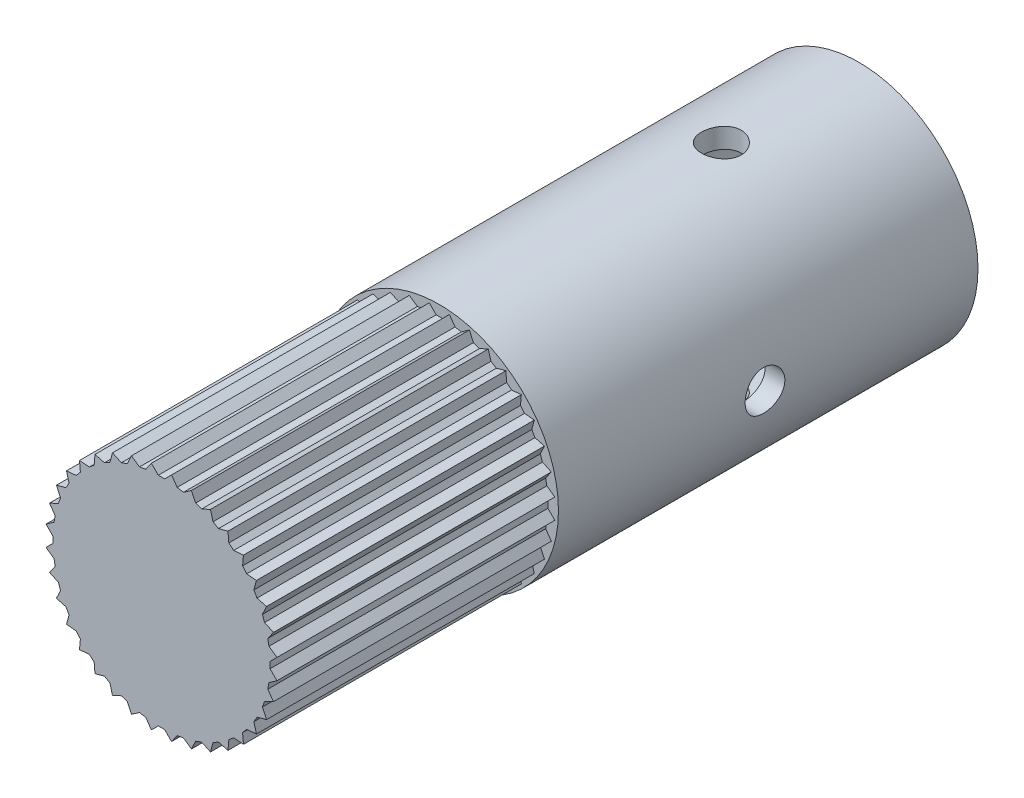
SolidWorks part; units mm, degrees
material "AISI 1015 Steel, Cold Drawn (SS)"
ref_plane "X-Y Datum" through (0, 0, 0) normal (0, 0, 1) x (1, 0, 0)
ref_plane "X-Z Datum" through (0, 0, 0) normal (0, 1, 0) x (1, 0, 0)
ref_plane "Y-Z Datum" through (0, 0, 0) normal (1, 0, 0) x (0, 0, -1)
sketch "Sketch9" plane through (0, 0, 0) normal (0, 1, 0) x (1, 0, 0)
  line L0 (16.002, 0) -> (0, 0)
  line L1 (0, 0) -> (0, -389.0916)
  line L2 (0, -389.0916) -> (-72.2493, -524.9728)
  dimension "D1" = 153.895
  dimension "D2" = 28
  dimension "D3" = 389.0916
  dimension "D5" = 16.002
sketch "Sketch5" plane through (0, 0, 0) normal (0, 1, 0) x (1, 0, 0)
  line L0 (7.9375, -77.9416) -> (7.9375, -22.1615)
  line L1 (7.9375, -22.1615) -> (9.525, -22.1615)
  line L2 (9.525, -22.1615) -> (9.525, -77.9416)
  line L3 (9.525, -77.9416) -> (7.9375, -77.9416)
  line L5 (16.002, 0) -> (0, 0) construction
  line L6 (0, 0) -> (0, -389.0916) construction
  line L7 (0, -389.0916) -> (9.525, -389.0916) construction
  line L8 (12.5602, -58.6916) -> (0, -58.6916) construction
  dimension "D1" = 1.5875
  dimension "D2" = 22.1615
  dimension "D3" = 7.9375
  dimension "D4" = 330.4
  dimension "D5" = 311.15
revolve "Revolve2" add sketch "Sketch5" angle 360 about L1
sketch "Sketch6" plane through (0, 0, 0) normal (0, 1, 0) x (1, 0, 0)
  circle A0 centre (0, -33.1635) radius 1.5875 construction
  circle A1 centre (0, -33.1635) radius 1.5875
sketch "Sketch7" plane through (0, 0, 0) normal (1, 0, 0) x (0, 0, -1)
  circle A2 centre (-39.196, 0) radius 1.5875
  circle A4 centre (-39.196, 0) radius 1.5875 construction
extrude "Cut-Extrude5" cut sketch "Sketch7" against normal through all both and the other way through all
extrude "Cut-Extrude6" cut sketch "Sketch6" against normal through all both and the other way through all
sketch "Sketch8" plane through (0, 0, 0) normal (0, 0, 1) x (1, 0, 0)
  line L0 (9.2357, -0.808) -> (8.6817, -0.254)
  line L1 (8.6817, -0.254) -> (8.6817, 0.254)
  line L2 (8.6817, 0.254) -> (9.2357, 0.808)
  line L3 (8.6817, 0) -> (0, 0) construction
  line L4 (8.9551, -2.3995) -> (8.5057, -1.7577)
  line L5 (8.5057, -1.7577) -> (8.5939, -1.2574)
  line L6 (8.5939, -1.2574) -> (9.2357, -0.808)
  line L7 (8.4024, -3.9181) -> (8.0713, -3.208)
  line L8 (8.0713, -3.208) -> (8.245, -2.7306)
  line L9 (8.245, -2.7306) -> (8.9551, -2.3995)
  line L10 (7.5944, -5.3176) -> (7.3916, -4.5608)
  line L11 (7.3916, -4.5608) -> (7.6456, -4.1209)
  line L12 (7.6456, -4.1209) -> (8.4024, -3.9181)
  line L13 (6.5556, -6.5556) -> (6.4873, -5.7751)
  line L14 (6.4873, -5.7751) -> (6.8138, -5.3859)
  line L15 (6.8138, -5.3859) -> (7.5944, -5.3176)
  line L16 (5.3176, -7.5944) -> (5.3859, -6.8138)
  line L17 (5.3859, -6.8138) -> (5.7751, -6.4873)
  line L18 (5.7751, -6.4873) -> (6.5556, -6.5556)
  line L19 (3.9181, -8.4024) -> (4.1209, -7.6456)
  line L20 (4.1209, -7.6456) -> (4.5608, -7.3916)
  line L21 (4.5608, -7.3916) -> (5.3176, -7.5944)
  line L22 (2.3995, -8.9551) -> (2.7306, -8.245)
  line L23 (2.7306, -8.245) -> (3.208, -8.0713)
  line L24 (3.208, -8.0713) -> (3.9181, -8.4024)
  line L25 (0.808, -9.2357) -> (1.2574, -8.5939)
  line L26 (1.2574, -8.5939) -> (1.7577, -8.5057)
  line L27 (1.7577, -8.5057) -> (2.3995, -8.9551)
  line L28 (-0.808, -9.2357) -> (-0.254, -8.6817)
  line L29 (-0.254, -8.6817) -> (0.254, -8.6817)
  line L30 (0.254, -8.6817) -> (0.808, -9.2357)
  line L31 (-2.3995, -8.9551) -> (-1.7577, -8.5057)
  line L32 (-1.7577, -8.5057) -> (-1.2574, -8.5939)
  line L33 (-1.2574, -8.5939) -> (-0.808, -9.2357)
  line L34 (-3.9181, -8.4024) -> (-3.208, -8.0713)
  line L35 (-3.208, -8.0713) -> (-2.7306, -8.245)
  line L36 (-2.7306, -8.245) -> (-2.3995, -8.9551)
  line L37 (-5.3176, -7.5944) -> (-4.5608, -7.3916)
  line L38 (-4.5608, -7.3916) -> (-4.1209, -7.6456)
  line L39 (-4.1209, -7.6456) -> (-3.9181, -8.4024)
  line L40 (-6.5556, -6.5556) -> (-5.7751, -6.4873)
  line L41 (-5.7751, -6.4873) -> (-5.3859, -6.8138)
  line L42 (-5.3859, -6.8138) -> (-5.3176, -7.5944)
  line L43 (-7.5944, -5.3176) -> (-6.8138, -5.3859)
  line L44 (-6.8138, -5.3859) -> (-6.4873, -5.7751)
  line L45 (-6.4873, -5.7751) -> (-6.5556, -6.5556)
  line L46 (-8.4024, -3.9181) -> (-7.6456, -4.1209)
  line L47 (-7.6456, -4.1209) -> (-7.3916, -4.5608)
  line L48 (-7.3916, -4.5608) -> (-7.5944, -5.3176)
  line L49 (-8.9551, -2.3995) -> (-8.245, -2.7306)
  line L50 (-8.245, -2.7306) -> (-8.0713, -3.208)
  line L51 (-8.0713, -3.208) -> (-8.4024, -3.9181)
  line L52 (-9.2357, -0.808) -> (-8.5939, -1.2574)
  line L53 (-8.5939, -1.2574) -> (-8.5057, -1.7577)
  line L54 (-8.5057, -1.7577) -> (-8.9551, -2.3995)
  line L55 (-9.2357, 0.808) -> (-8.6817, 0.254)
  line L56 (-8.6817, 0.254) -> (-8.6817, -0.254)
  line L57 (-8.6817, -0.254) -> (-9.2357, -0.808)
  line L58 (-8.9551, 2.3995) -> (-8.5057, 1.7577)
  line L59 (-8.5057, 1.7577) -> (-8.5939, 1.2574)
  line L60 (-8.5939, 1.2574) -> (-9.2357, 0.808)
  line L61 (-8.4024, 3.9181) -> (-8.0713, 3.208)
  line L62 (-8.0713, 3.208) -> (-8.245, 2.7306)
  line L63 (-8.245, 2.7306) -> (-8.9551, 2.3995)
  line L64 (-7.5944, 5.3176) -> (-7.3916, 4.5608)
  line L65 (-7.3916, 4.5608) -> (-7.6456, 4.1209)
  line L66 (-7.6456, 4.1209) -> (-8.4024, 3.9181)
  line L67 (-6.5556, 6.5556) -> (-6.4873, 5.7751)
  line L68 (-6.4873, 5.7751) -> (-6.8138, 5.3859)
  line L69 (-6.8138, 5.3859) -> (-7.5944, 5.3176)
  line L70 (-5.3176, 7.5944) -> (-5.3859, 6.8138)
  line L71 (-5.3859, 6.8138) -> (-5.7751, 6.4873)
  line L72 (-5.7751, 6.4873) -> (-6.5556, 6.5556)
  line L73 (-3.9181, 8.4024) -> (-4.1209, 7.6456)
  line L74 (-4.1209, 7.6456) -> (-4.5608, 7.3916)
  line L75 (-4.5608, 7.3916) -> (-5.3176, 7.5944)
  line L76 (-2.3995, 8.9551) -> (-2.7306, 8.245)
  line L77 (-2.7306, 8.245) -> (-3.208, 8.0713)
  line L78 (-3.208, 8.0713) -> (-3.9181, 8.4024)
  line L79 (-0.808, 9.2357) -> (-1.2574, 8.5939)
  line L80 (-1.2574, 8.5939) -> (-1.7577, 8.5057)
  line L81 (-1.7577, 8.5057) -> (-2.3995, 8.9551)
  line L82 (0.808, 9.2357) -> (0.254, 8.6817)
  line L83 (0.254, 8.6817) -> (-0.254, 8.6817)
  line L84 (-0.254, 8.6817) -> (-0.808, 9.2357)
  line L85 (2.3995, 8.9551) -> (1.7577, 8.5057)
  line L86 (1.7577, 8.5057) -> (1.2574, 8.5939)
  line L87 (1.2574, 8.5939) -> (0.808, 9.2357)
  line L88 (3.9181, 8.4024) -> (3.208, 8.0713)
  line L89 (3.208, 8.0713) -> (2.7306, 8.245)
  line L90 (2.7306, 8.245) -> (2.3995, 8.9551)
  line L91 (5.3176, 7.5944) -> (4.5608, 7.3916)
  line L92 (4.5608, 7.3916) -> (4.1209, 7.6456)
  line L93 (4.1209, 7.6456) -> (3.9181, 8.4024)
  line L94 (6.5556, 6.5556) -> (5.7751, 6.4873)
  line L95 (5.7751, 6.4873) -> (5.3859, 6.8138)
  line L96 (5.3859, 6.8138) -> (5.3176, 7.5944)
  line L97 (7.5944, 5.3176) -> (6.8138, 5.3859)
  line L98 (6.8138, 5.3859) -> (6.4873, 5.7751)
  line L99 (6.4873, 5.7751) -> (6.5556, 6.5556)
  line L100 (8.4024, 3.9181) -> (7.6456, 4.1209)
  line L101 (7.6456, 4.1209) -> (7.3916, 4.5608)
  line L102 (7.3916, 4.5608) -> (7.5944, 5.3176)
  line L103 (8.9551, 2.3995) -> (8.245, 2.7306)
  line L104 (8.245, 2.7306) -> (8.0713, 3.208)
  line L105 (8.0713, 3.208) -> (8.4024, 3.9181)
  line L106 (9.2357, 0.808) -> (8.5939, 1.2574)
  line L107 (8.5939, 1.2574) -> (8.5057, 1.7577)
  line L108 (8.5057, 1.7577) -> (8.9551, 2.3995)
  circle A0 centre (0, 0) radius 12.7
  circle A1 centre (0, 0) radius 9.271 construction
  circle A2 centre (0, 0) radius 8.6854 construction
  point P153 (0, 0)
  dimension "D1" = 25.4
  dimension "D4" = 18.542
  dimension "D6" = 17.3708
  dimension "D2" = 0.508
  dimension "D3" = 135
  dimension "D5" = 36
extrude "Cut-Extrude7" cut sketch "Sketch8" against normal blind 22.225 from surface starting at face at (-9.525, 0, 77.9416)
ref_plane "Plane1" through (0, 0, 47.5615) normal (0, 0, -1) x (-1, 0, 0)
sketch "Sketch10" plane through (0, 0, 47.5615) normal (0, 0, -1) x (-1, 0, 0)
  circle A0 centre (0, 0) radius 7.9375
  dimension "D1" = 15.875
extrude "Boss-Extrude1" add sketch "Sketch10" against normal up to surface (30.3801 mm away) up to face at (-7.9375, 0, 77.9416)
sketch "Sketch11" plane through (0, 0, 22.1615) normal (0, 0, -1) x (-1, 0, 0)
  line L0 (0, 9.525) -> (13.3548, 9.525) construction
  line L1 (0, 9.525) -> (0, 15.4312) construction
  line L2 (-9.525, 0) -> (-9.525, 9.1744) construction
  line L3 (-9.525, 0) -> (-16.674, 0) construction
  circle A0 centre (0, 0) radius 9.525 construction
  point P0 (0, 9.525)
  point P1 (-9.525, 0)
